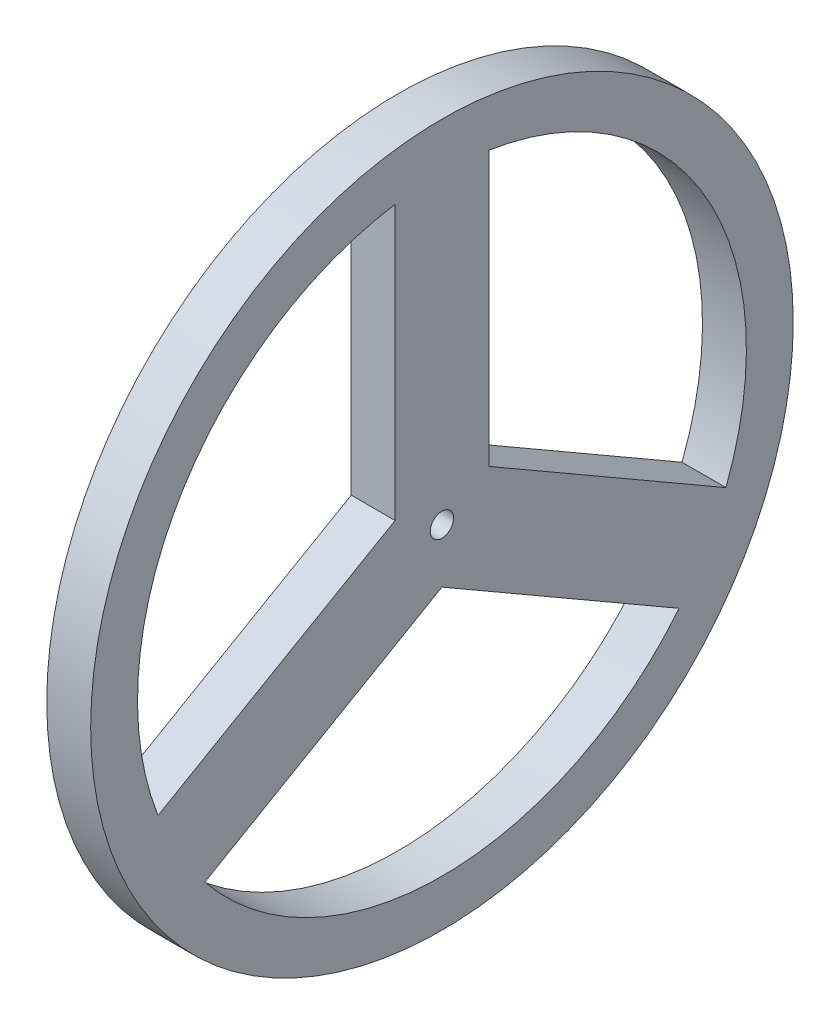
SolidWorks part; units mm, degrees
material "Corrugated Paper"
ref_plane "Front Plane" through (0, 0, 0) normal (0, 0, 1) x (1, 0, 0)
ref_plane "Top Plane" through (0, 0, 0) normal (0, 1, 0) x (1, 0, 0)
ref_plane "Right Plane" through (0, 0, 0) normal (1, 0, 0) x (0, 0, -1)
sketch "Sketch2" plane through (0, 0, 0) normal (1, 0, 0) x (0, 0, -1)
  line L0 (0, 33.02) -> (0, 0) construction
  line L1 (0, 0) -> (28.5962, -16.51) construction
  line L2 (0, 0) -> (-28.5962, -16.51) construction
  line L3 (-2.54, -4.3994) -> (26.0562, -20.9094)
  line L4 (-2.54, 4.3994) -> (-31.1362, -12.1106)
  line L5 (-5.08, 33.02) -> (-5.08, 0)
  line L6 (2.54, 4.3994) -> (31.1362, -12.1106)
  line L7 (2.54, -4.3994) -> (-26.0562, -20.9094)
  line L8 (5.08, 33.02) -> (5.08, 0)
  circle A0 centre (0, 0) radius 38.1
  circle A1 centre (0, 0) radius 33.02
  circle A2 centre (0, 0) radius 5.08
  circle A3 centre (0, 0) radius 1.27
  dimension "D1" = 76.2
  dimension "D3" = 10.16
  dimension "D4" = 2.54
  dimension "D5" = 120
  dimension "D6" = 120
  dimension "D2" = 5.08
  dimension "D7" = 5.08
  dimension "D8" = 5.08
extrude "Boss-Extrude5" add sketch "Sketch2" along normal blind 4.7625 contours A0
extrude "Cut-Extrude3" cut sketch "Sketch2<3>" along direction (1, 0, 0) on the side of the normal through all contours L7 A1 L3 | L5 A1 L4 | L6 A1 L8 | A3 region at (0, -21.1007, 0) region at (0, 10.5503, 18.2737) region at (0, 10.5503, -18.2737) region at (0, 0, 0)
sketch "Sketch2<3>" plane through (0, 0, 0) normal (1, 0, 0) x (0, 0, -1) same geometry as "Sketch2"
equation "\"rodThick\"= 0.1in"
equation "\"thick\"= 3/16in"
equation "\"D1@Boss-Extrude5\"=\"thick\""
equation "\"D4@Sketch2\"=\"rodThick\""
